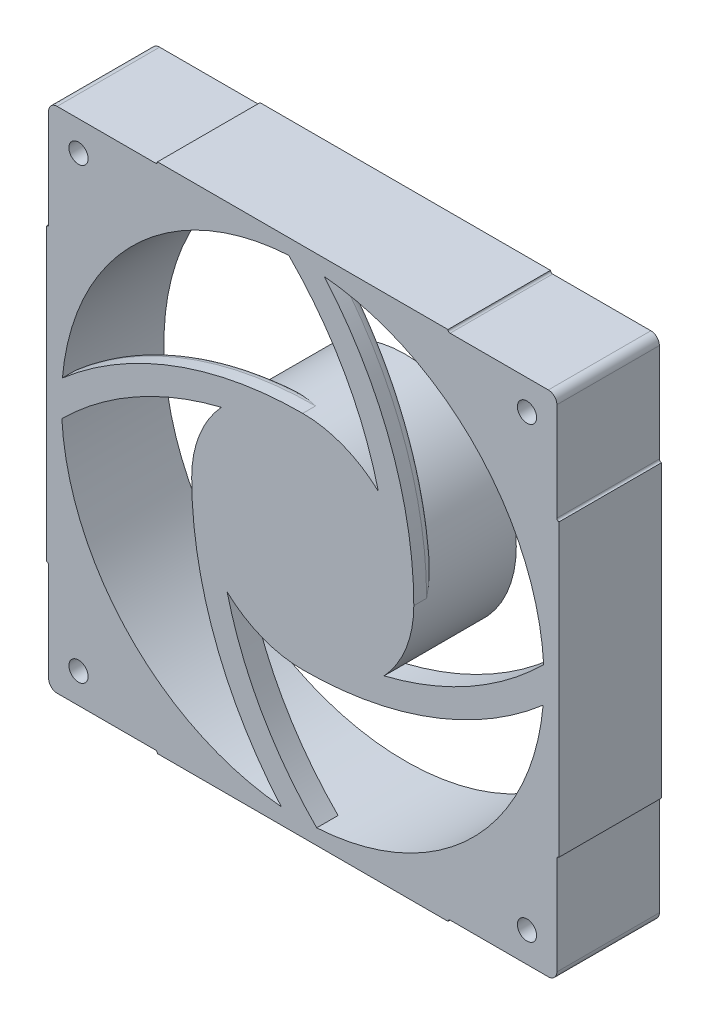
SolidWorks part; units mm, degrees
ref_plane "Plan de face" through (0, 0, 0) normal (0, 0, 1) x (1, 0, 0)
ref_plane "Plan de dessus" through (0, 0, 0) normal (0, 1, 0) x (1, 0, 0)
ref_plane "Plan de droite" through (0, 0, 0) normal (1, 0, 0) x (0, 0, -1)
sketch "Esquisse1" plane through (0, 0, 0) normal (0, 0, 1) x (1, 0, 0)
  line L0 (0, 120) -> (120, 0) construction
  line L1 (0, 0) -> (120, 0)
  line L2 (0, 0) -> (0, 120)
  line L3 (0, 120) -> (120, 120)
  line L4 (120, 0) -> (120, 120)
  line L5 (0, 60) -> (120, 60) construction
  line L6 (0, 120) -> (0.4, 120)
  line L7 (0, 120) -> (0, 95)
  line L10 (60, 120) -> (60, 0) construction
  line L14 (0, 120) -> (32.1134, 120)
  line L15 (0, 120) -> (0, 114.3424)
  circle A0 centre (60, 60) radius 56.5
  circle A1 centre (60, 60) radius 26
  dimension "D3" = 113
  dimension "D4" = 52
  dimension "D1" = 120
  dimension "D2" = 120
extrude "Boss.-Extru.1" add sketch "Esquisse1" along normal blind 24 contours L1 L4 L3 L7 L2 A0 | A1 region at (1.6971, 47.5, 0) region at (60, 60, 0)
sketch "Esquisse2" plane through (0, 0, 24) normal (0, 0, 1) x (1, 0, 0)
  line L0 (0, 94) -> (0.5, 94)
  line L1 (0, 0) -> (0, 120) construction
  line L2 (0.5, 94) -> (0.5, 119.5)
  line L3 (0.5, 119.5) -> (26, 119.5)
  line L4 (26, 119.5) -> (26, 120)
  line L5 (0, 120) -> (120, 120) construction
  line L6 (0, 94) -> (0, 120)
  line L7 (0, 120) -> (26, 120)
  line L8 (60, 0) -> (60, 120) construction
  line L9 (0, 0) -> (120, 0) construction
  line L10 (0, 60) -> (120, 60) construction
  line L11 (120, 0) -> (120, 120) construction
  line L12 (26, 0.5) -> (26, 0)
  line L13 (0, 26) -> (0.5, 26)
  line L14 (0.5, 26) -> (0.5, 0.5)
  line L15 (0.5, 0.5) -> (26, 0.5)
  line L16 (0, 26) -> (0, 0)
  line L17 (0, 0) -> (26, 0)
  line L18 (120, 0) -> (94, 0)
  line L19 (120, 26) -> (120, 0)
  line L20 (119.5, 0.5) -> (94, 0.5)
  line L21 (119.5, 26) -> (119.5, 0.5)
  line L22 (120, 26) -> (119.5, 26)
  line L23 (94, 0.5) -> (94, 0)
  line L24 (120, 120) -> (94, 120)
  line L25 (120, 94) -> (120, 120)
  line L26 (94, 119.5) -> (94, 120)
  line L27 (119.5, 119.5) -> (94, 119.5)
  line L28 (119.5, 94) -> (119.5, 119.5)
  line L29 (120, 94) -> (119.5, 94)
  point P4 (26, 119.75)
  dimension "D1" = 26
  dimension "D2" = 0.5
extrude "Enlèv. mat.-Extru.1" cut sketch "Esquisse2" against normal through all
fillet "Congé1" radius 0.5 8 edges at (94, 119.5, 12) (119.5, 94, 12) (94, 0.5, 12) (119.5, 26, 12) (26, 0.5, 12) (0.5, 26, 12) (0.5, 94, 12) (26, 119.5, 12)
fillet "Congé2" radius 2 4 edges at (0.5, 0.5, 12) (119.5, 0.5, 12) (119.5, 119.5, 12) (0.5, 119.5, 12)
sketch "Esquisse3" plane through (0, 0, 24) normal (0, 0, 1) x (1, 0, 0)
  line L0 (86, 60) -> (34, 60) construction
  line L1 (120, 26) -> (120, 94) construction
  line L2 (58.3883, 0) -> (67.085, 0)
  line L3 (26, 0) -> (94, 0) construction
  line L4 (0, 61.6117) -> (0, 52.915)
  line L5 (61.6117, 120) -> (52.915, 120)
  line L6 (120, 58.3883) -> (120, 67.085)
  circle A0 centre (60, 60) radius 26 construction
  arc A1 (34, 60) -> (58.3883, 0) centre (120, 60) ccw
  arc A2 (42.3, 40.9551) -> (67.085, 0) centre (120, 60) ccw
  circle A3 centre (60, 60) radius 26
  arc A4 (60, 86) -> (0, 61.6117) centre (60, 0) ccw
  arc A5 (40.9551, 77.7) -> (0, 52.915) centre (60, 0) ccw
  arc A6 (86, 60) -> (61.6117, 120) centre (0, 60) ccw
  arc A7 (77.7, 79.0449) -> (52.915, 120) centre (0, 60) ccw
  arc A8 (60, 34) -> (120, 58.3883) centre (60, 120) ccw
  arc A9 (79.0449, 42.3) -> (120, 67.085) centre (60, 120) ccw
  circle A10 centre (60, 60) radius 56.5
  point P9 (60, 60)
  point P33 (60, 60)
  circle M26 centre (60, 60) radius 56.5
  dimension "D1" = 172
  dimension "D2" = 6
  dimension "D4" = 113
  dimension "D3" = 4
extrude "Boss.-Extru.2" add sketch "Esquisse3" against normal blind 5 contours A5 A3 A4 M26 | A7 A3 A6 M26 | A9 A3 A8 M26 | A3 A1 A2 M26 region at (46.3222, 24.3002, 24) region at (24.3002, 73.6778, 24) region at (95.6998, 46.3222, 24) region at (73.6778, 95.6998, 24)
fillet "Congé3" radius 2 4 edges at (39.4125, 29.9724, 19) (29.9724, 80.5875, 19) (80.5875, 90.0276, 19) (90.0276, 39.4125, 19)
sketch "Esquisse4" plane through (0, 0, 0) normal (0, 0, -1) x (-1, 0, 0)
  line L0 (-0.5, 94.5) -> (-0.5, 117.5) construction
  line L1 (-2.5, 119.5) -> (-25.5, 119.5) construction
  line L2 (-60, 0) -> (-60, 120) construction
  line L3 (-26, 0) -> (-94, 0) construction
  line L4 (-26, 120) -> (-94, 120) construction
  line L5 (0, 26) -> (0, 94) construction
  line L6 (0, 60) -> (-120, 60) construction
  line L7 (-120, 26) -> (-120, 94) construction
  circle A0 centre (-7.5, 112.5) radius 2.25
  circle A1 centre (-112.5, 112.5) radius 2.25
  circle A2 centre (-7.5, 7.5) radius 2.25
  circle A3 centre (-112.5, 7.5) radius 2.25
  dimension "D1" = 4.5
  dimension "D2" = 7
  dimension "D3" = 7
extrude "Enlèv. mat.-Extru.2" cut sketch "Esquisse4" against normal through all
